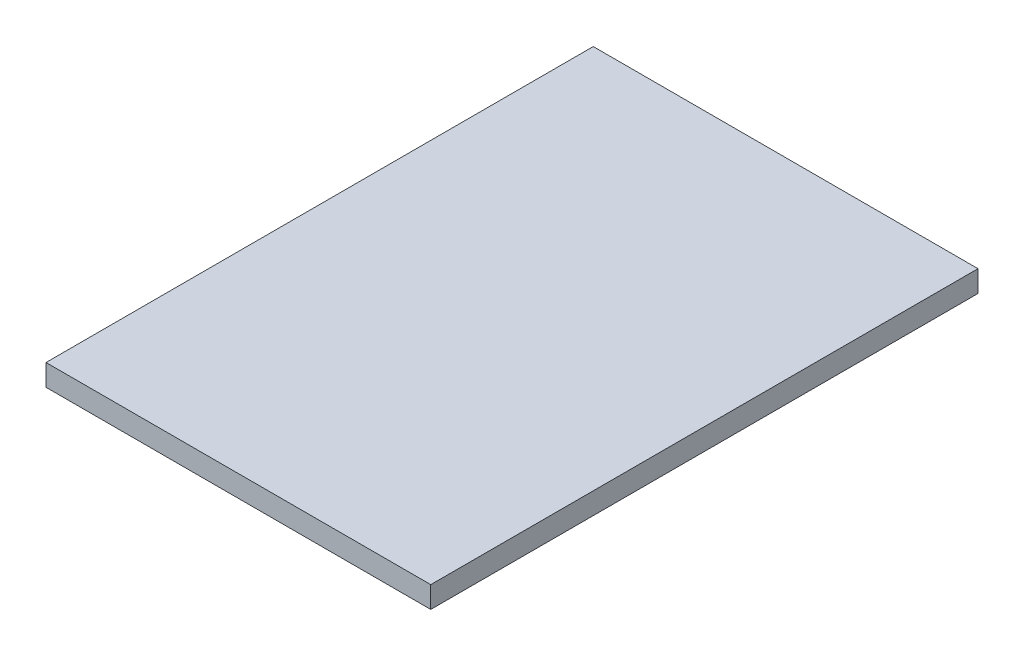
SolidWorks part; units mm, degrees
material "Perspex (TM) GS Acrylic Cast Sheet"
ref_plane "Front Plane" through (0, 0, 0) normal (0, 0, 1) x (1, 0, 0)
ref_plane "Top Plane" through (0, 0, 0) normal (0, 1, 0) x (1, 0, 0)
ref_plane "Right Plane" through (0, 0, 0) normal (1, 0, 0) x (0, 0, -1)
sketch "Sketch1" plane through (0, 0, 0) normal (0, 1, 0) x (1, 0, 0)
  line L1 (-80.5, -114.5) -> (80.5, -114.5)
  line L2 (-80.5, -114.5) -> (-80.5, 114.5)
  line L3 (-80.5, 114.5) -> (80.5, 114.5)
  line L4 (80.5, -114.5) -> (80.5, 114.5)
  line L5 (-80.5, -114.5) -> (80.5, 114.5) construction
  line L6 (-80.5, 114.5) -> (80.5, -114.5) construction
  point P0 (0, 0)
  dimension "D1" = 161
  dimension "D2" = 229
extrude "Boss-Extrude1" add sketch "Sketch1" along normal blind 9
sketch "Sketch2" plane through (0, 9, 0) normal (0, 1, 0) x (1, 0, 0)
  line L14 (-71.5, -105.5) -> (71.5, -105.5)
  line L15 (71.5, -105.5) -> (71.5, 105.5)
  line L16 (71.5, 105.5) -> (-71.5, 105.5)
  line L17 (-71.5, 105.5) -> (-71.5, -105.5)
  line L18 (-71.5, -105.5) -> (71.5, -105.5)
  line L19 (71.5, -105.5) -> (71.5, 105.5)
  line L20 (71.5, 105.5) -> (-71.5, 105.5)
  line L21 (-71.5, 105.5) -> (-71.5, -105.5)
  dimension "D1" = 9
equation "\"PCLength\"= 143mm'Length across I/O from PS to GPU"
equation "\"PCWidth\"= 340mm'Distance of longest part parallel to GPU(ussually GPU)"
equation "\"PCHeight\"= 190mm'Tallest point with mobo laying flat"
equation "\"WallThickness\"= 9mm'Thickness of each outer tank wall"
equation "\"ThermoBarrierThickness\"= 6mm'Thickness of barrier between hot side and cold side"
equation "\"HotSideGap\"= 15mm'Space in the hot side that hot fluid flows into"
equation "\"PCClearance\"= 40mm'Clearance from top of tank to top of PC"
equation "\"RadiatorHeight\"= 277.37mm'Final Height from ground of radiators"
equation "\"AirflowGap\"= 26mm'Distance between radiators and tank for airflow"
equation "\"VolumeSubtraction\"= 230mm"
equation "\"D1@Sketch1\"=\"PCLength\" + (2 * \"WallThickness\")"
equation "\"D1@Boss-Extrude1\"=\"WallThickness\""
equation "\"D2@Sketch1\"=\"PCHeight\" + \"ThermoBarrierThickness\" + \"HotSideGap\" + (2 * \"WallThickness\")"
